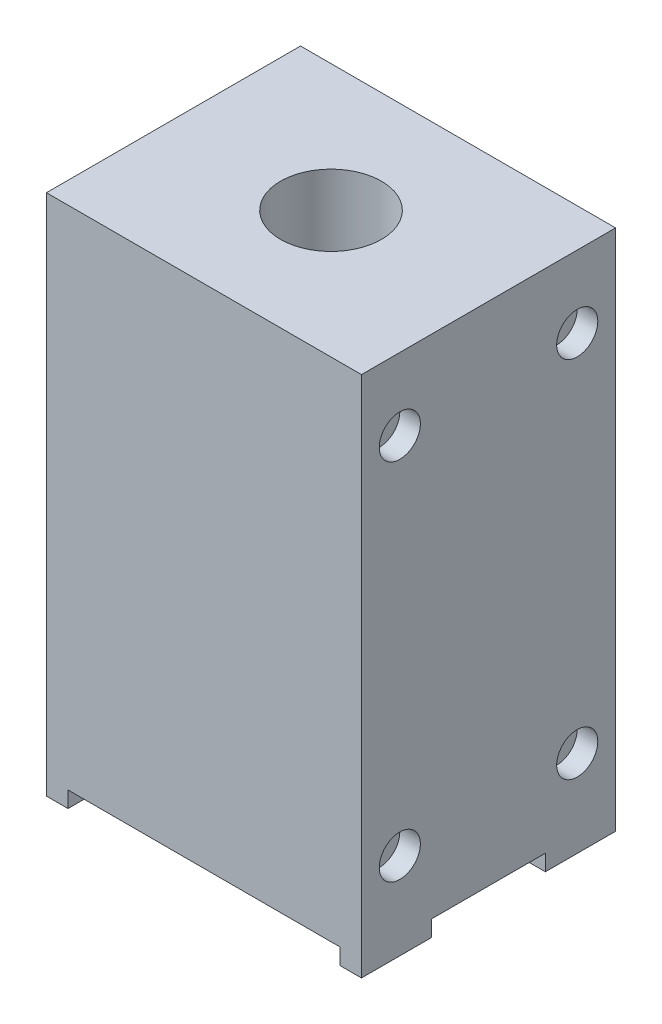
SolidWorks part; units mm, degrees
ref_plane "Front Plane" through (0, 0, 0) normal (0, 0, 1) x (1, 0, 0)
ref_plane "Top Plane" through (0, 0, 0) normal (0, 1, 0) x (1, 0, 0)
ref_plane "Right Plane" through (0, 0, 0) normal (1, 0, 0) x (0, 0, -1)
sketch "Sketch2" plane through (0, 0, 0) normal (0, 1, 0) x (1, 0, 0)
  line L1 (-15.325, 12.36) -> (15.325, 12.36)
  line L2 (-15.325, 12.36) -> (-15.325, -12.36)
  line L3 (-15.325, -12.36) -> (15.325, -12.36)
  line L4 (15.325, 12.36) -> (15.325, -12.36)
  line L5 (-15.325, 12.36) -> (15.325, -12.36) construction
  line L6 (-15.325, -12.36) -> (15.325, 12.36) construction
  point P0 (0, 0)
  dimension "D1" = 24.72
  dimension "D2" = 30.65
extrude "Boss-Extrude1" add sketch "Sketch2" along normal blind 49.27
sketch "Sketch12" plane through (0, 0, 0) normal (0, -1, 0) x (1, 0, 0)
  line L1 (-15.325, 12.36) -> (-13.225, 12.36)
  line L2 (-15.325, 12.36) -> (-15.325, 5.53)
  line L3 (-15.325, 5.53) -> (-13.225, 5.53)
  line L4 (-13.225, 12.36) -> (-13.225, 5.53)
  line L5 (-15.325, -12.36) -> (-13.225, -12.36)
  line L6 (-15.325, -12.36) -> (-15.325, -5.53)
  line L7 (-15.325, -5.53) -> (-13.225, -5.53)
  line L8 (-13.225, -12.36) -> (-13.225, -5.53)
  line L9 (15.325, 12.36) -> (13.225, 12.36)
  line L10 (15.325, 12.36) -> (15.325, 5.53)
  line L11 (15.325, 5.53) -> (13.225, 5.53)
  line L12 (13.225, 12.36) -> (13.225, 5.53)
  line L13 (15.325, -12.36) -> (13.225, -12.36)
  line L14 (15.325, -12.36) -> (15.325, -5.53)
  line L15 (15.325, -5.53) -> (13.225, -5.53)
  line L16 (13.225, -12.36) -> (13.225, -5.53)
  dimension "D1" = 6.83
  dimension "D2" = 6.83
  dimension "D3" = 6.83
  dimension "D4" = 6.83
  dimension "D5" = 2.1
  dimension "D6" = 2.1
  dimension "D7" = 2.1
  dimension "D8" = 2.1
extrude "Boss-Extrude2" add sketch "Sketch12" along normal blind 1.57
sketch "Sketch4" plane through (0, 49.27, 0) normal (0, 1, 0) x (1, 0, 0)
  circle A0 centre (0, 0) radius 4.91
  dimension "D1" = 9.82
extrude "Cut-Extrude3" cut sketch "Sketch4" against normal blind 22
sketch "Sketch5" plane through (0, 27.27, 0) normal (0, 1, 0) x (1, 0, 0)
  circle A0 centre (0, 0) radius 2
  dimension "D1" = 4
extrude "Cut-Extrude4" cut sketch "Sketch5" against normal blind 5
sketch "Sketch7" plane through (0, 22.27, 0) normal (0, 1, 0) x (1, 0, 0)
  circle A0 centre (0, 0) radius 1.5
  dimension "D1" = 3
extrude "Cut-Extrude5" cut sketch "Sketch7" against normal through all
fillet "Fillet4" radius 3 1 edges at (0, 27.27, 2) first distance on face at (0, 27.27, 2)
fillet "Fillet5" radius 3 1 edges at (0, 22.27, 1.5) first distance on face at (0, 22.27, 1.5)
sketch "Sketch13" plane through (15.325, 0, 0) normal (1, 0, 0) x (0, 0, -1)
  line L0 (-12.36, 49.27) -> (12.36, 49.27) construction
  line L1 (-12.36, 49.27) -> (-12.36, -1.57) construction
  line L2 (12.36, 49.27) -> (12.36, -1.57) construction
  line L3 (12.36, -1.57) -> (5.53, -1.57) construction
  line L4 (-5.53, -1.57) -> (-12.36, -1.57) construction
  circle A0 centre (-8.63, 42.27) radius 2
  circle A1 centre (8.63, 42.27) radius 2
  circle A2 centre (-8.63, 6.87) radius 2
  circle A3 centre (8.63, 6.87) radius 2
  dimension "D1" = 4
  dimension "D2" = 4
  dimension "D3" = 4
  dimension "D4" = 4
  dimension "D5" = 7
  dimension "D6" = 7
  dimension "D7" = 3.73
  dimension "D8" = 3.73
  dimension "D9" = 8.44
  dimension "D10" = 8.44
  dimension "D11" = 3.73
  dimension "D12" = 3.73
extrude "Cut-Extrude6" cut sketch "Sketch13" against normal blind 2
sketch "Sketch14" plane through (15.325, 0, 0) normal (1, 0, 0) x (0, 0, -1)
  line L0 (0, 49.27) -> (0, 0) construction
  line L1 (-12.36, 49.27) -> (12.36, 49.27) construction
equation "\"3。21\"=4.09161"
